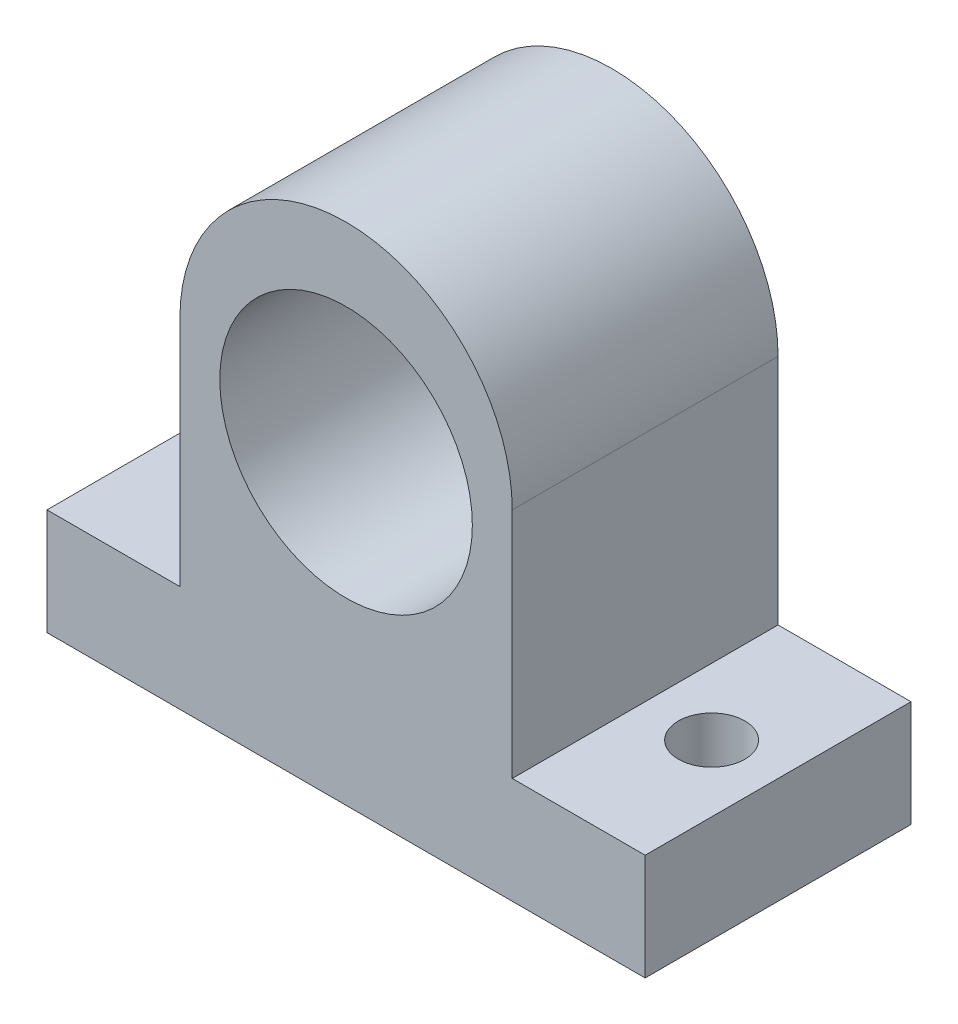
SolidWorks part; units mm, degrees
material "ABS"
ref_plane "Front Plane" through (0, 0, 0) normal (0, 0, 1) x (1, 0, 0)
ref_plane "Top Plane" through (0, 0, 0) normal (0, 1, 0) x (1, 0, 0)
ref_plane "Right Plane" through (0, 0, 0) normal (1, 0, 0) x (0, 0, -1)
sketch "Sketch2" plane through (0, 0, 0) normal (0, 1, 0) x (1, 0, 0)
  line L1 (-22.5, 10) -> (22.5, 10)
  line L2 (-22.5, 10) -> (-22.5, -10)
  line L3 (-22.5, -10) -> (22.5, -10)
  line L4 (22.5, 10) -> (22.5, -10)
  line L5 (-22.5, 10) -> (22.5, -10) construction
  line L6 (-22.5, -10) -> (22.5, 10) construction
  point P0 (0, 0)
  dimension "D1" = 45
  dimension "D2" = 20
extrude "Boss-Extrude1" add sketch "Sketch2" along normal blind 8
sketch "Sketch3" plane through (0, 8, 0) normal (0, 1, 0) x (1, 0, 0)
  line L1 (-12.5, 10) -> (12.5, 10)
  line L2 (-12.5, 10) -> (-12.5, -10)
  line L3 (-12.5, -10) -> (12.5, -10)
  line L4 (12.5, 10) -> (12.5, -10)
  line L5 (-12.5, 10) -> (12.5, -10) construction
  line L6 (-12.5, -10) -> (12.5, 10) construction
  point P0 (0, 0)
  dimension "D1" = 20
  dimension "D2" = 25
extrude "Boss-Extrude2" add sketch "Sketch3" along normal blind 30
sketch "Sketch4" plane through (0, 8, 0) normal (0, 1, 0) x (1, 0, 0)
  line L0 (-12.5, 10) -> (-22.5, 10) construction
  line L1 (-22.5, 10) -> (-22.5, -10) construction
  line L3 (22.5, 10) -> (12.5, 10) construction
  line L4 (22.5, -10) -> (22.5, 10) construction
  circle A0 centre (-17.5, 0) radius 2.5
  circle A1 centre (17.5, 0) radius 2.5
  dimension "D1" = 5
  dimension "D2" = 5
  dimension "D3" = 10
  dimension "D4" = 5
  dimension "D5" = 10
  dimension "D6" = 5
extrude "Cut-Extrude1" cut sketch "Sketch4" against normal up to surface (8 mm away) up to face at (0, 0, 0)
sketch "Sketch5" plane through (0, 0, 10) normal (0, 0, 1) x (1, 0, 0)
  line L0 (-22.5, 0) -> (22.5, 0) construction
  line L2 (-12.5, 38) -> (-12.5, 8) construction
  circle A0 centre (0, 23) radius 9.5
  dimension "D3" = 19
  dimension "D1" = 23
  dimension "D2" = 12.5
extrude "Cut-Extrude2" cut sketch "Sketch5" against normal up to surface (20 mm away) up to face at (0, 13.5, -10)
fillet "Fillet2" 2 edges at (-12.5, 38, 0) (12.5, 38, 0) type full round first side face at (-12.5, 23, 0) second side face at (12.5, 23, 0) middle face at (0, 38, 0)
